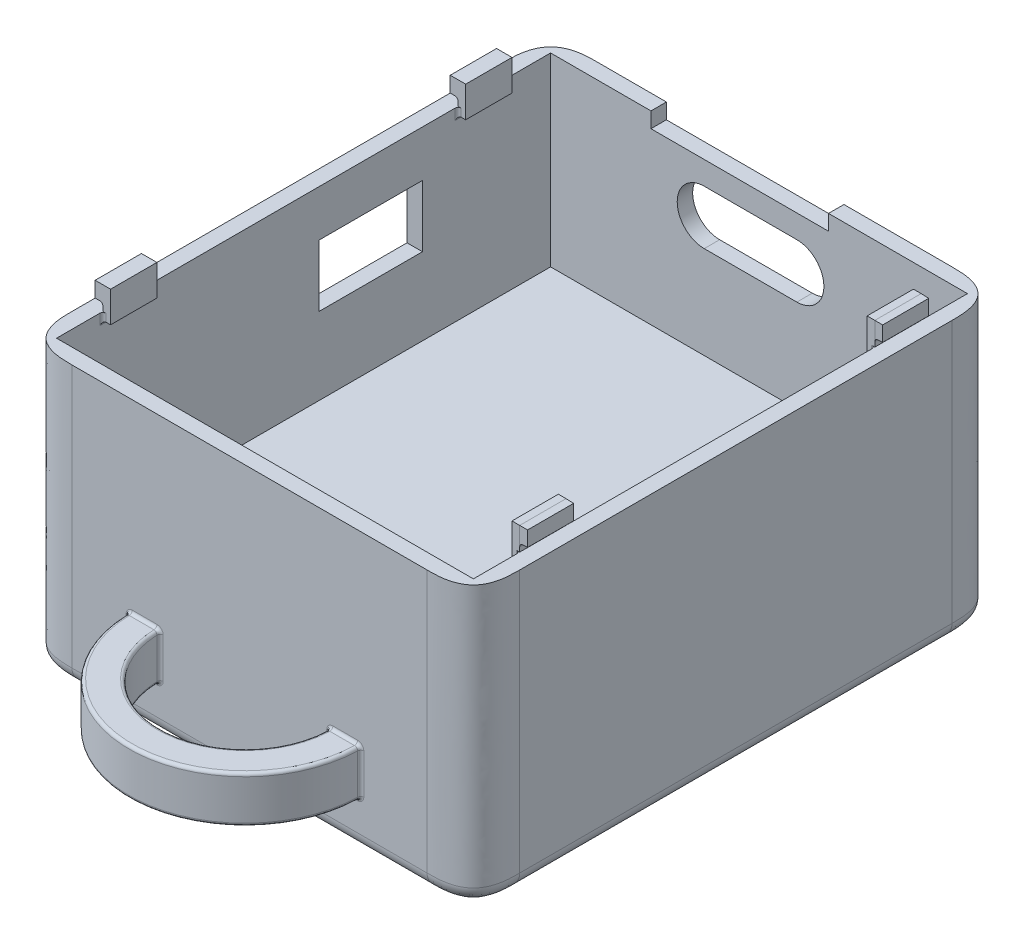
SolidWorks part; units mm, degrees
ref_plane "Front Plane" through (0, 0, 0) normal (0, 0, 1) x (1, 0, 0)
ref_plane "Top Plane" through (0, 0, 0) normal (0, 1, 0) x (1, 0, 0)
ref_plane "Right Plane" through (0, 0, 0) normal (1, 0, 0) x (0, 0, -1)
sketch "Sketch1" plane through (0, 0, 0) normal (0, 1, 0) x (1, 0, 0)
  line L1 (-148.5843, 96.7753) -> (-119.5843, 96.7753)
  line L2 (-148.5843, 96.7753) -> (-148.5843, 62.7753)
  line L3 (-148.5843, 62.7753) -> (-119.5843, 62.7753)
  line L4 (-119.5843, 96.7753) -> (-119.5843, 62.7753)
  dimension "D1" = 29
  dimension "D2" = 34
extrude "Bottom-Extrude" add sketch "Sketch1" along normal blind 18
fillet "Sid_Corner-Fillet" radius 3 4 edges at (-119.5843, 9, -62.7753) (-148.5843, 9, -62.7753) (-119.5843, 9, -96.7753) (-148.5843, 9, -96.7753) curvature continuous yes
fillet "Bottom-Fillet" radius 1 8 edges
sketch "Sketch2" plane through (0, 18, 0) normal (0, 1, 0) x (1, 0, 0)
  line L0 (-122.5843, 96.7753) -> (-145.5843, 96.7753) construction
  line L1 (-147.5843, 95.7753) -> (-120.5843, 95.7753)
  line L2 (-147.5843, 95.7753) -> (-147.5843, 63.7753)
  line L3 (-147.5843, 63.7753) -> (-120.5843, 63.7753)
  line L4 (-120.5843, 95.7753) -> (-120.5843, 63.7753)
  line L5 (-145.5843, 62.7753) -> (-122.5843, 62.7753) construction
  line L6 (-148.5843, 93.7753) -> (-148.5843, 65.7753) construction
  line L7 (-119.5843, 65.7753) -> (-119.5843, 93.7753) construction
  dimension "D1" = 1
  dimension "D2" = 1
  dimension "D3" = 1
  dimension "D4" = 1
extrude "Cut-Extrude1" cut sketch "Sketch2" against normal blind 12
ref_plane "Plane7" through (0, 0, -62.7753) normal (0, 0, 1) x (1, 0, 0)
ref_plane "Plane8" through (0, 1, 0) normal (0, 1, 0) x (1, 0, 0)
ref_plane "Plane9" through (0, 3, 0) normal (0, -1, 0) x (-1, 0, 0)
sketch "Sketch21" plane through (0, 3, 0) normal (0, -1, 0) x (-1, 0, 0)
  line L0 (-7.8811, 62.7753) -> (7.8811, 62.7753) construction
  line L1 (141.8802, 62.7753) -> (126.8802, 62.7753)
  arc A0 (126.8802, 62.7753) -> (141.8802, 62.7753) centre (134.3802, 62.7753) ccw
  arc A1 (128.8802, 62.7753) -> (139.8802, 62.7753) centre (134.3802, 62.7753) ccw
  dimension "D1" = 15
  dimension "D2" = 2
  dimension "D3" = 5.5
extrude "Boss-Extrude1" add sketch "Sketch21" against normal blind 3 contours A1 L1 A0 region at (-134.3802, 3, -55.443)
fillet "Fillet1" radius 0.2 12 edges at (-139.8802, 4.5, -62.7753) (-128.8802, 4.5, -62.7753) (-127.8802, 6, -62.7753) (-140.8802, 6, -62.7753) (-134.3802, 6, -57.2753) (-141.8802, 4.5, -62.7753) (-134.3802, 6, -55.2753) (-126.8802, 4.5, -62.7753) (-140.8802, 3, -62.7753) (-134.3802, 3, -55.2753) (-127.8802, 3, -62.7753) (-134.3802, 3, -57.2753)
sketch "Sketch22" plane through (0, 0, -96.7753) normal (0, 0, -1) x (-1, 0, 0)
  line L0 (131.6343, 13.75) -> (137.6343, 13.75) construction
  line L1 (131.6343, 15.5) -> (137.6343, 15.5)
  line L2 (131.6343, 12) -> (137.6343, 12)
  line L3 (122.5843, 18) -> (122.5843, 1) construction
  line L5 (145.5843, 1) -> (145.5843, 18) construction
  line L6 (122.5843, 18) -> (145.5843, 18) construction
  line L8 (129.5843, 18) -> (141.0843, 18)
  line L9 (129.5843, 18) -> (129.5843, 17)
  line L10 (129.5843, 17) -> (141.0843, 17)
  line L11 (141.0843, 18) -> (141.0843, 17)
  arc A0 (131.6343, 15.5) -> (131.6343, 12) centre (131.6343, 13.75) ccw
  arc A1 (137.6343, 12) -> (137.6343, 15.5) centre (137.6343, 13.75) ccw
  point P2 (134.6343, 13.75)
  dimension "D1" = 6
  dimension "D3" = 9.05
  dimension "D4" = 2.5
  dimension "D5" = 7.95
  dimension "D2" = 3.5
  dimension "D6" = 11.5
  dimension "D7" = 7
  dimension "D8" = 1
  dimension "D9" = 1.5
extrude "Cut-USB" cut sketch "Sketch22" against normal up to next
sketch "Sketch23" plane through (-148.5843, 0, 0) normal (-1, 0, 0) x (0, 0, 1)
  line L0 (-65.7753, 1) -> (-65.7753, 18) construction
  line L1 (-87.4753, 15) -> (-80.7753, 15)
  line L2 (-87.4753, 15) -> (-87.4753, 11)
  line L3 (-87.4753, 11) -> (-80.7753, 11)
  line L4 (-80.7753, 15) -> (-80.7753, 11)
  line L5 (-93.7753, 18) -> (-65.7753, 18) construction
  dimension "D1" = 4
  dimension "D2" = 6.7
  dimension "D3" = 15
  dimension "D4" = 3
extrude "Cut-BT" cut sketch "Sketch23" against normal up to surface (1 mm away) up to face at (-147.5843, 12, -79.7753)
sketch "Sketch24" plane through (-120.5843, 0, 0) normal (-1, 0, 0) x (0, 0, 1)
  line L0 (-63.7753, 18) -> (-95.7753, 18) construction
  line L1 (-69.7753, 19.5) -> (-66.7753, 19.5)
  line L2 (-69.7753, 19.5) -> (-69.7753, 17.5)
  line L3 (-69.7753, 17.5) -> (-66.7753, 17.5)
  line L4 (-66.7753, 19.5) -> (-66.7753, 17.5)
  line L5 (-63.7753, 6) -> (-63.7753, 18) construction
  dimension "D1" = 3
  dimension "D2" = 2
  dimension "D3" = 0.5
  dimension "D4" = 3
extrude "Boss-Clip" add sketch "Sketch24" along normal blind 0.5
sketch "Sketch26" plane through (-120.5843, 0, 0) normal (1, 0, 0) x (0, 0, -1)
  line L0 (66.7753, 18) -> (66.7753, 19.5) construction
  line L1 (66.7753, 19.5) -> (69.7753, 19.5)
  line L2 (66.7753, 19.5) -> (66.7753, 18.5)
  line L3 (66.7753, 18.5) -> (69.7753, 18.5)
  line L4 (69.7753, 19.5) -> (69.7753, 18.5)
  line L5 (69.7753, 19.5) -> (69.7753, 18) construction
  line L6 (66.7753, 19.5) -> (69.7753, 19.5) construction
  dimension "D1" = 3
  dimension "D2" = 1
  dimension "D3" = 0
extrude "Boss-ClipExt" add sketch "Sketch26" along normal blind 0.5 draft 1
fillet "Fillet2" radius 0.2 4 edges at (-120.5843, 17.75, -69.7753) (-120.5843, 17.75, -66.7753) (-120.5843, 17.5, -68.2753) (-120.5843, 18.5, -68.2753)
pattern_linear "LPattern2" count 2 spacing 23 along (0, 0, -1) of "Boss-Clip", "Boss-ClipExt", "Fillet2"
sketch "Sketch27" plane through (-147.5843, 0, 0) normal (1, 0, 0) x (0, 0, -1)
  line L0 (95.7753, 18) -> (63.7753, 18) construction
  line L1 (66.7753, 19.5) -> (69.7753, 19.5)
  line L2 (66.7753, 19.5) -> (66.7753, 17.5)
  line L3 (66.7753, 17.5) -> (69.7753, 17.5)
  line L4 (69.7753, 19.5) -> (69.7753, 17.5)
  line L5 (63.7753, 6) -> (63.7753, 18) construction
  dimension "D1" = 3
  dimension "D2" = 2
  dimension "D3" = 0.5
  dimension "D4" = 3
extrude "Boss-Clip1" add sketch "Sketch27" along normal blind 0.5
sketch "Sketch28" plane through (-147.5843, 0, 0) normal (-1, 0, 0) x (0, 0, 1)
  line L0 (-66.7753, 19.5) -> (-66.7753, 18) construction
  line L1 (-69.7753, 19.5) -> (-66.7753, 19.5)
  line L2 (-69.7753, 19.5) -> (-69.7753, 18.5)
  line L3 (-69.7753, 18.5) -> (-66.7753, 18.5)
  line L4 (-66.7753, 19.5) -> (-66.7753, 18.5)
  dimension "D1" = 1
  dimension "D2" = 0
extrude "Boss-ClipExt1" add sketch "Sketch28" along normal blind 0.5
fillet "Fillet4" radius 0.2 4 edges at (-147.5843, 18.5, -68.2753) (-147.5843, 17.75, -69.7753) (-147.5843, 17.5, -68.2753) (-147.5843, 17.75, -66.7753)
pattern_linear "LPattern4" count 2 spacing 23 along (0, 0, -1) of "Boss-Clip1", "Boss-ClipExt1", "Fillet4"
